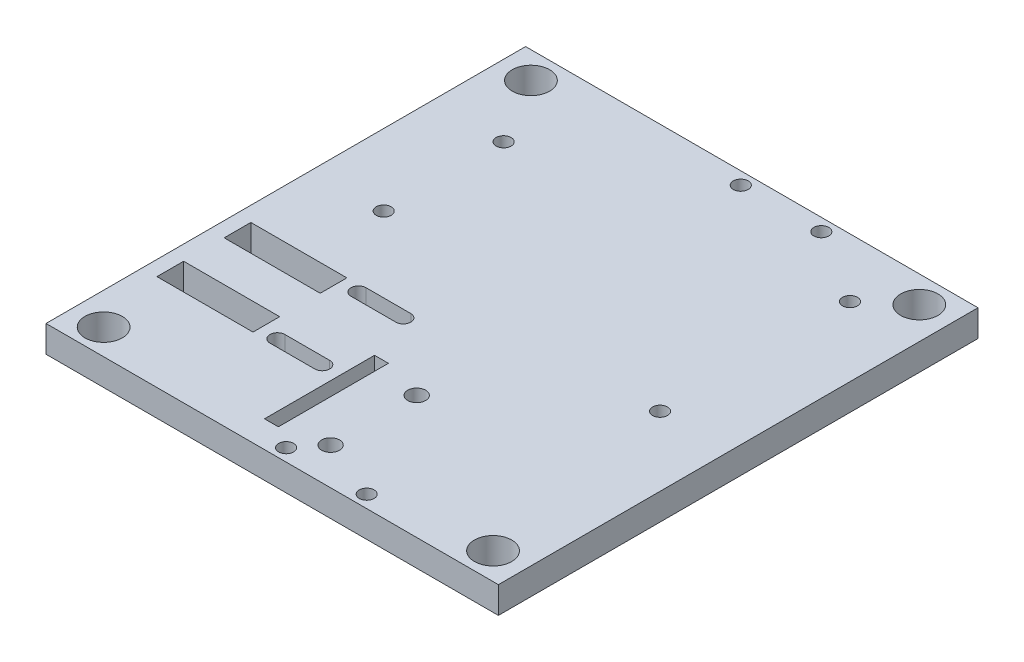
SolidWorks part; units mm, degrees
material "ABS"
ref_plane "Plan de face" through (0, 0, 0) normal (0, 0, 1) x (1, 0, 0)
ref_plane "Plan de dessus" through (0, 0, 0) normal (0, 1, 0) x (1, 0, 0)
ref_plane "Plan de droite" through (0, 0, 0) normal (1, 0, 0) x (0, 0, -1)
sketch "Esquisse1" plane through (0, 0, 0) normal (0, 1, 0) x (1, 0, 0)
  line L0 (-55, 0) -> (55, 0) construction
  line L1 (-53.848, 57.0865) -> (53.848, 57.0865)
  line L2 (-53.848, 57.0865) -> (-53.848, -57.0865)
  line L3 (-53.848, -57.0865) -> (53.848, -57.0865)
  line L4 (53.848, 57.0865) -> (53.848, -57.0865)
  line L5 (-53.848, 57.0865) -> (53.848, -57.0865) construction
  line L6 (-53.848, -57.0865) -> (53.848, 57.0865) construction
  line L7 (-8.1788, -25.3365) -> (-4.8768, -25.3365)
  line L8 (-8.1788, -25.3365) -> (-8.1788, -50.7365)
  line L9 (-8.1788, -50.7365) -> (-4.8768, -50.7365)
  line L10 (-4.8768, -25.3365) -> (-4.8768, -50.7365)
  line L11 (-8.1788, -25.3365) -> (-4.8768, -50.7365) construction
  line L12 (-8.1788, -50.7365) -> (-4.8768, -25.3365) construction
  line L13 (-50.292, -11.8745) -> (-27.432, -11.8745)
  line L14 (-50.292, -11.8745) -> (-50.292, -18.2245)
  line L15 (-50.292, -18.2245) -> (-27.432, -18.2245)
  line L16 (-27.432, -11.8745) -> (-27.432, -18.2245)
  line L17 (-50.292, -11.8745) -> (-27.432, -18.2245) construction
  line L18 (-50.292, -18.2245) -> (-27.432, -11.8745) construction
  line L19 (-50.292, -27.8765) -> (-27.432, -27.8765)
  line L20 (-50.292, -27.8765) -> (-50.292, -34.2265)
  line L21 (-50.292, -34.2265) -> (-27.432, -34.2265)
  line L22 (-27.432, -27.8765) -> (-27.432, -34.2265)
  line L23 (-50.292, -27.8765) -> (-27.432, -34.2265) construction
  line L24 (-50.292, -34.2265) -> (-27.432, -27.8765) construction
  line L25 (-23.1394, -34.4805) -> (-12.4714, -34.4805)
  line L27 (-23.1394, -30.9245) -> (-12.4714, -30.9245)
  line L29 (-12.4714, -30.9245) -> (-12.4714, -34.4805) construction
  line L30 (-12.4714, -34.4805) -> (-23.1394, -30.9245) construction
  line L31 (-23.1394, -30.9245) -> (-23.1394, -34.4805) construction
  line L32 (-23.1394, -15.1765) -> (-12.4714, -15.1765)
  line L33 (-23.1394, -11.6205) -> (-12.4714, -11.6205)
  line L34 (-12.4714, -11.6205) -> (-12.4714, -15.1765) construction
  line L35 (-12.4714, -15.1765) -> (-23.1394, -11.6205) construction
  line L36 (-23.1394, -11.6205) -> (-23.1394, -15.1765) construction
  line L37 (-23.1394, -15.1765) -> (-12.4714, -11.6205) construction
  line L38 (-23.1394, -34.4805) -> (-12.4714, -30.9245) construction
  line L39 (-38.862, -15.0495) -> (-38.862, -31.0515) construction
  line L40 (-17.8054, -32.7025) -> (-17.8054, -13.3985) construction
  line L41 (-27.432, -27.8765) -> (-17.8054, -27.8765) construction
  line L42 (-17.8054, -27.8765) -> (-8.1788, -27.8765) construction
  circle A0 centre (0.3429, -54.1147) radius 1.778
  circle A1 centre (19.5199, -54.1147) radius 1.778
  circle A2 centre (6.858, -49.9745) radius 1.778
  circle A3 centre (6.858, -30.6705) radius 1.778
  circle A4 centre (-4.572, -23.0505) radius 1.778
  circle A5 centre (46.228, -50.7365) radius 4.445
  circle A6 centre (46.228, 50.7365) radius 4.445
  circle A9 centre (37.338, 43.1165) radius 1.778
  circle A10 centre (37.338, -2.0955) radius 1.778
  circle A11 centre (-36.83, 34.8361) radius 1.778
  circle A12 centre (-36.83, 6.2865) radius 1.778
  circle A13 centre (19.5199, 54.1147) radius 1.778
  circle A14 centre (0.3429, 54.1147) radius 1.778
  circle A15 centre (-46.228, 50.7365) radius 4.445
  circle A16 centre (-46.228, -50.9905) radius 4.445
  arc A19 (-23.1394, -30.9245) -> (-23.1394, -34.4805) centre (-23.1394, -32.7025) ccw
  arc A20 (-12.4714, -34.4805) -> (-12.4714, -30.9245) centre (-12.4714, -32.7025) ccw
  arc A21 (-23.1394, -11.6205) -> (-23.1394, -15.1765) centre (-23.1394, -13.3985) ccw
  arc A22 (-12.4714, -15.1765) -> (-12.4714, -11.6205) centre (-12.4714, -13.3985) ccw
  point P0 (0, 0)
  point P10 (-6.5278, -50.7365)
  point P11 (-6.5278, -38.0365)
  point P64 (-17.8054, -32.7025)
  point P65 (-17.8054, -13.3985)
  point P70 (-17.8054, -23.0505)
  point P71 (-38.862, -23.0505)
  dimension "D5" = 3.556
  dimension "D12" = 3.556
  dimension "D14" = 46.99
  dimension "D15" = 58.42
  dimension "D16" = 3.556
  dimension "D17" = 34.036
  dimension "D18" = 8.89
  dimension "D20" = 6.35
  dimension "D21" = 3.556
  dimension "D22" = 16.51
  dimension "D27" = 74.168
  dimension "D29" = 9.652
  dimension "D35" = 7.62
  dimension "D36" = 6.35
  dimension "D34" = 8.89
  dimension "D31" = 8.89
  dimension "D41" = 3.556
  dimension "D1" = 107.696
  dimension "D2" = 114.173
  dimension "D3" = 34.3281
  dimension "D4" = 19.177
  dimension "D6" = 2.9718
  dimension "D7" = 6.35
  dimension "D8" = 58.7248
  dimension "D9" = 25.4
  dimension "D10" = 3.302
  dimension "D11" = 19.304
  dimension "D13" = 7.112
  dimension "D19" = 7.62
  dimension "D23" = 13.97
  dimension "D24" = 45.212
  dimension "D25" = 8.2804
  dimension "D26" = 8.382
  dimension "D28" = 22.86
  dimension "D30" = 81.28
  dimension "D32" = 6.35
  dimension "D33" = 22.86
  dimension "D37" = 7.62
  dimension "D38" = 6.35
  dimension "D39" = 7.62
  dimension "D40" = 6.096
  dimension "D42" = 10.668
  dimension "D43" = 19.304
extrude "Boss.-Extru.1" add sketch "Esquisse1" along normal blind 6.35 contours L2 L3 L4 L1
extrude "Enlèv. mat.-Extru.3" cut sketch "Esquisse1<6>" along normal through all flip side to cut
sketch "Esquisse1<6>" plane through (0, 0, 0) normal (0, 1, 0) x (1, 0, 0) same geometry as "Esquisse1"
sketch "Esquisse2" plane through (0, 6.35, 0) normal (0, 1, 0) x (1, 0, 0)
  circle A0 centre (-4.572, -23.0505) radius 1.778
  circle A1 centre (6.858, -30.6705) radius 1.778
  circle A2 centre (6.858, -49.9745) radius 1.778
extrude "Boss.-Extru.2" add sketch "Esquisse2" against normal up to surface (6.35 mm away) up to face at (-46.228, 0, 55.4355)
sketch "Esquisse3" plane through (0, 6.35, 0) normal (0, 1, 0) x (1, 0, 0)
  line L1 (-8.1788, -25.3365) -> (-4.8768, -25.3365)
  line L2 (-8.1788, -25.3365) -> (-8.1788, -24.5428)
  line L3 (-8.1788, -24.5428) -> (-4.8768, -24.5428)
  line L4 (-4.8768, -25.3365) -> (-4.8768, -24.5428)
  circle A0 centre (5.0992, -27.7865) radius 2.135
  circle A1 centre (5.0992, -48.2865) radius 2.135
  dimension "D1" = 4.27
  dimension "D2" = 4.27
  dimension "D3" = 0.7937
extrude "Enlèv. mat.-Extru.4" cut sketch "Esquisse3" against normal through all
